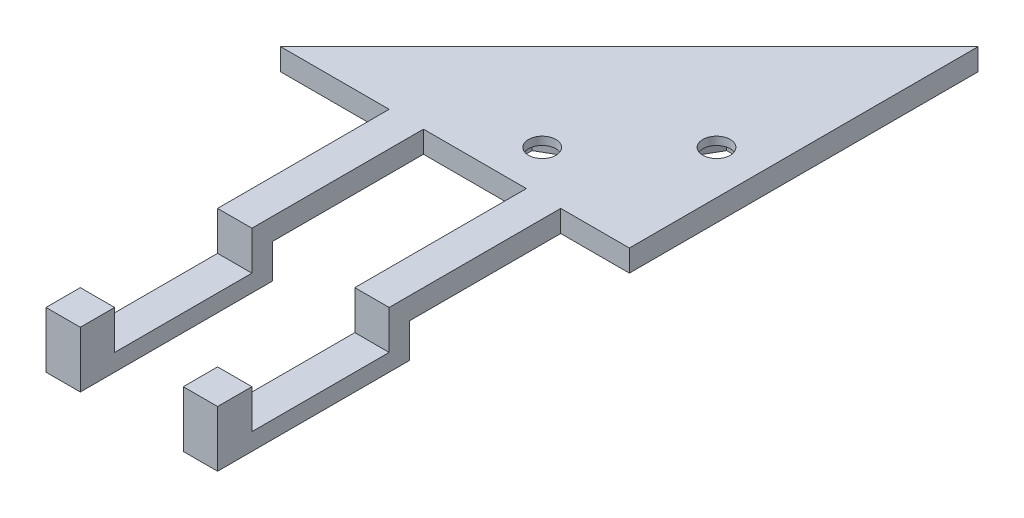
SolidWorks part; units mm, degrees
ref_plane "Front" through (0, 0, 0) normal (0, 0, 1) x (1, 0, 0)
ref_plane "Top" through (0, 0, 0) normal (0, 1, 0) x (1, 0, 0)
ref_plane "Right" through (0, 0, 0) normal (1, 0, 0) x (0, 0, -1)
sketch "Sketch1" plane through (0, 0, 0) normal (0, 1, 0) x (1, 0, 0)
  line L0 (0, 0) -> (50.8, 0)
  line L1 (-55, 0) -> (55, 0) construction
  line L2 (50.8, 0) -> (0, 50.8)
  line L3 (0, -55) -> (0, 55) construction
  line L4 (0, 50.8) -> (0, 0)
  dimension "D1" = 50.8
  dimension "D2" = 50.8
extrude "Boss-Extrude1" add sketch "Sketch1" along normal blind 3.175 contours L2 L4 L0
sketch "Sketch2" plane through (0, 3.175, 0) normal (0, 1, 0) x (1, 0, 0)
  line L0 (0, -55) -> (0, 55) construction
  line L1 (-55, 0) -> (55, 0) construction
  line L2 (0, 0) -> (25.4, 25.4) construction
  line L3 (50.8, 0) -> (0, 50.8) construction
  circle A0 centre (19.05, 6.35) radius 2
  circle A1 centre (6.35, 19.05) radius 2
  dimension "D1" = 4
  dimension "D3" = 6.35
  dimension "D2" = 19.05
extrude "Cut-Extrude1" cut sketch "Sketch2" against normal through all contours A0 | A1
sketch "Sketch3" plane through (0, 3.175, 0) normal (0, 1, 0) x (1, 0, 0)
  line L0 (0, 0) -> (25.4, 25.4) construction
  line L1 (8.3707, 15.55) -> (10.3914, 19.05)
  line L2 (10.3914, 19.05) -> (8.3707, 22.55)
  line L3 (0, 0) -> (50.8, 0)
  line L4 (50.8, 0) -> (0, 50.8)
  line L5 (0, 50.8) -> (0, 0)
  line L6 (0, 0) -> (50.8, 0)
  line L7 (50.8, 0) -> (0, 50.8)
  line L8 (0, 50.8) -> (0, 0)
  line L9 (8.3707, 22.55) -> (4.3293, 22.55)
  line L10 (4.3293, 22.55) -> (2.3086, 19.05)
  line L11 (2.3086, 19.05) -> (4.3293, 15.55)
  line L12 (4.3293, 15.55) -> (8.3707, 15.55)
  line L13 (22.55, 4.3293) -> (19.05, 2.3086)
  line L14 (19.05, 2.3086) -> (15.55, 4.3293)
  line L15 (15.55, 4.3293) -> (15.55, 8.3707)
  line L16 (15.55, 8.3707) -> (19.05, 10.3914)
  line L17 (19.05, 10.3914) -> (22.55, 8.3707)
  line L18 (22.55, 8.3707) -> (22.55, 4.3293)
  circle A0 centre (6.35, 19.05) radius 2 construction
  circle A1 centre (6.35, 19.05) radius 2
  circle A2 centre (19.05, 6.35) radius 2 construction
  circle A3 centre (19.05, 6.35) radius 2
  circle A4 centre (6.35, 19.05) radius 3.5 construction
  dimension "D2" = 7
  dimension "D1" = 0
extrude "Cut-Extrude2" cut sketch "Sketch3" along normal blind 2 from surface contours L2 L9 L10 L11 L12 L1 | L17 L18 L13 L14 L15 L16 starting at face at (6.35, 0, -21.05)
sketch "Sketch5" plane through (0, 0, 0) normal (1, 0, 0) x (0, 0, -1)
  line L0 (0, 4.4963) -> (0, -4.4963) construction
  line L1 (0, 3.175) -> (-25, 3.175)
  line L2 (0, 3.175) -> (0, 0)
  line L3 (0, 0) -> (-25, 0)
  line L4 (-25, 3.175) -> (-25, 0)
  line L5 (0, 3.175) -> (50.8, 3.175) construction
  line L6 (27.94, 0) -> (-27.94, 0) construction
  line L11 (-45, 0) -> (-50, 0)
  line L12 (-45, 0) -> (-45, 3.175)
  line L13 (-45, 3.175) -> (-50, 3.175)
  line L14 (-50, 0) -> (-50, 3.175)
  line L15 (-50, 0) -> (-22, 0)
  line L16 (-50, 0) -> (-50, -5)
  line L17 (-50, -5) -> (-22, -5)
  line L18 (-22, 0) -> (-22, -5)
  line L20 (-45, 0) -> (-25, 0)
  line L21 (-45, 0) -> (-45, -2.5)
  line L22 (-45, -2.5) -> (-25, -2.5)
  line L23 (-25, 0) -> (-25, -2.5)
  dimension "D1" = 3.175
  dimension "D2" = 25
  dimension "D3" = 5
  dimension "D4" = 25
  dimension "D5" = 3
  dimension "D6" = 5
  dimension "D7" = 2.5
extrude "Boss-Extrude2" add sketch "Sketch5" along normal blind 5 from offset 10 contours L14 L11 L12 L13 | L18 L3 L15 L11 L16 L17 | L1 L4 L3 L2 region at (0, 1.5875, 12.5) region at (0, -3.1944, 36.5556) region at (0, 1.5875, 47.5)
extrude "Boss-Extrude3" add sketch "Sketch5<3>" along normal blind 5 from offset 30 contours L18 L3 L15 L11 L16 L17 | L1 L4 L3 L2 | L13 L14 L11 L12 region at (0, 1.5875, 12.5) region at (0, -3.1944, 36.5556)
sketch "Sketch5<3>" plane through (0, 0, 0) normal (1, 0, 0) x (0, 0, -1) same geometry as "Sketch5"
mirror "Mirror1" about plane through (0, 0, 0) normal (1, 0, 0) of bodies 105
sketch "Sketch6" plane through (0, 0, 0) normal (0, 1, 0) x (1, 0, 0)
  line L0 (0, -4.4963) -> (0, 4.4963) construction
  line L1 (0, 54.0374) -> (50.944, 54.0374)
  line L2 (0, 54.0374) -> (0, -54.3147)
  line L3 (0, -54.3147) -> (50.944, -54.3147)
  line L4 (50.944, 54.0374) -> (50.944, -54.3147)
extrude "Cut-Extrude3" cut sketch "Sketch6" against normal through all both and the other way through all
